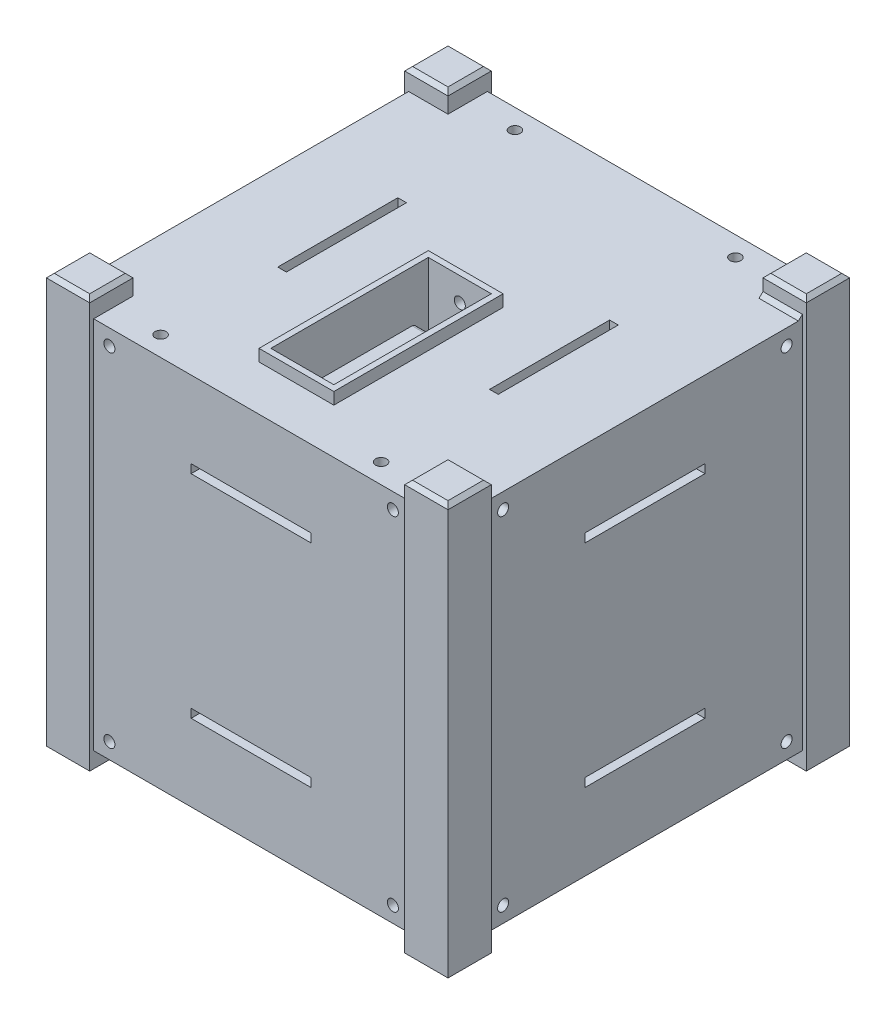
SolidWorks part; units mm, degrees
ref_plane "Front Plane" through (0, 0, 0) normal (0, 0, 1) x (1, 0, 0)
ref_plane "Top Plane" through (0, 0, 0) normal (0, 1, 0) x (1, 0, 0)
ref_plane "Right Plane" through (0, 0, 0) normal (1, 0, 0) x (0, 0, -1)
sketch "Sketch1" plane through (0, 0, 0) normal (0, 1, 0) x (1, 0, 0)
  line L1 (-50, 50) -> (50, 50)
  line L2 (-50, 50) -> (-50, -50)
  line L3 (-50, -50) -> (50, -50)
  line L4 (50, 50) -> (50, -50)
  line L5 (-50, 50) -> (50, -50) construction
  line L6 (-50, -50) -> (50, 50) construction
  point P0 (0, 0)
  dimension "D1" = 100
  dimension "D2" = 100
extrude "Boss-Extrude1" add sketch "Sketch1" along normal blind 95
ref_plane "Plane1" through (0, 100, 0) normal (0, 1, 0) x (1, 0, 0)
sketch "Sketch2" plane through (0, 100, 0) normal (0, 1, 0) x (1, 0, 0)
  line L0 (0, 0) -> (0, 71.0273) construction
  line L1 (-50, 50) -> (-40, 50)
  line L2 (-50, 50) -> (-50, 40)
  line L3 (-50, 40) -> (-40, 40)
  line L4 (-40, 50) -> (-40, 40)
  line L5 (50, 40) -> (40, 40)
  line L6 (40, 50) -> (40, 40)
  line L7 (50, 50) -> (40, 50)
  line L8 (50, 50) -> (50, 40)
  line L9 (0, 0) -> (-74.2097, 0) construction
  line L10 (50, -50) -> (50, -40)
  line L11 (50, -50) -> (40, -50)
  line L12 (40, -50) -> (40, -40)
  line L13 (50, -40) -> (40, -40)
  line L14 (-50, -40) -> (-40, -40)
  line L15 (-40, -50) -> (-40, -40)
  line L16 (-50, -50) -> (-40, -50)
  line L17 (-50, -50) -> (-50, -40)
  dimension "D1" = 10
  dimension "D2" = 10
extrude "Boss-Extrude2" add sketch "Sketch2" against normal blind 105
sketch "Sketch3" plane through (0, 95, 0) normal (0, 1, 0) x (1, 0, 0)
  line L0 (0, 0) -> (-55.4811, 0) construction
  line L1 (0, 0) -> (0, -56.887) construction
  line L3 (50, -40) -> (40, -40) construction
  circle A0 centre (-28, -45) radius 1.4
  circle A1 centre (28, -45) radius 1.4
  circle A2 centre (28, 45) radius 1.4
  circle A3 centre (-28, 45) radius 1.4
  dimension "D1" = 2.8
  dimension "D2" = 28
  dimension "D3" = 85
extrude "Cut-Extrude1" cut sketch "Sketch3" against normal blind 10
sketch "Sketch4" plane through (0, 100, 0) normal (0, 1, 0) x (1, 0, 0)
  line L0 (-50, 50) -> (-50, 40) construction
  line L1 (-40, 40) -> (-51, 40)
  line L2 (-40, 40) -> (-40, 51)
  line L3 (-40, 51) -> (-51, 51)
  line L4 (-51, 40) -> (-51, 51)
  line L5 (40, 50) -> (-40, 50) construction
  line L6 (0, 0) -> (0, 60.0537) construction
  line L7 (0, 0) -> (-61.4769, 0) construction
  line L8 (40, 51) -> (51, 51)
  line L9 (51, 40) -> (51, 51)
  line L10 (40, 40) -> (51, 40)
  line L11 (40, 40) -> (40, 51)
  line L12 (40, -40) -> (40, -51)
  line L13 (40, -40) -> (51, -40)
  line L14 (51, -40) -> (51, -51)
  line L15 (40, -51) -> (51, -51)
  line L16 (-40, -51) -> (-51, -51)
  line L17 (-51, -40) -> (-51, -51)
  line L18 (-40, -40) -> (-51, -40)
  line L19 (-40, -40) -> (-40, -51)
  dimension "D1" = 1
  dimension "D2" = 1
extrude "Boss-Extrude3" add sketch "Sketch4" against normal up to surface (105 mm away) up to face at (-45, -5, -45)
sketch "Sketch5" plane through (0, 0, 50) normal (0, 0, 1) x (1, 0, 0)
  line L0 (0, 95) -> (0, 43.7031) construction
  line L1 (-40, 95) -> (40, 95) construction
  line L2 (40, 47.5) -> (-59.8843, 47.5) construction
  line L3 (40, 0) -> (40, 95) construction
  line L4 (-40, 95) -> (-40, 0) construction
  circle A0 centre (-36, 91) radius 1.4
  circle A1 centre (36, 91) radius 1.4
  circle A2 centre (36, 4) radius 1.4
  circle A3 centre (-36, 4) radius 1.4
  dimension "D1" = 2.8
  dimension "D2" = 4
  dimension "D3" = 4
extrude "Cut-Extrude2" cut sketch "Sketch5" against normal blind 10
mirror "Mirror1" about plane through (0, 0, 0) normal (0, 0, 1) of "Cut-Extrude2"
sketch "Sketch6" plane through (-50, 0, 0) normal (-1, 0, 0) x (0, 0, 1)
  line L0 (-40, 95) -> (-40, 0) construction
  line L1 (-40, 95) -> (40, 95) construction
  line L2 (0, 95) -> (0, 40.4022) construction
  line L3 (-40, 47.5) -> (36.0105, 47.5) construction
  line L4 (-40, -5) -> (-40, 100) construction
  circle A0 centre (-36, 91) radius 1.4
  circle A1 centre (36, 91) radius 1.4
  circle A2 centre (36, 4) radius 1.4
  circle A3 centre (-36, 4) radius 1.4
  dimension "D1" = 2.8
  dimension "D2" = 4
  dimension "D3" = 4
extrude "Cut-Extrude3" cut sketch "Sketch6" against normal blind 10
mirror "Mirror2" about plane through (0, 0, 0) normal (1, 0, 0) of "Cut-Extrude3"
ref_plane "Plane2" through (0, 47.5, 0) normal (0, 1, 0) x (1, 0, 0)
mirror "Mirror3" about plane through (0, 47.5, 0) normal (0, 1, 0) of "Cut-Extrude1"
chamfer "Chamfer1" distance 1 angle 45 33 edges at (-45.5, -5, 51) (-40, -5, 45.5) (-45.5, -5, 40) (-51, -5, 45.5) (40, -5, 45.5) (45.5, -5, 51) (51, -5, 45.5) (45.5, -5, 40) (45.5, -5, -51) (40, -5, -45.5) (45.5, -5, -40) (51, -5, -45.5) (-40, -5, -45.5) (-45.5, -5, -51) (-51, -5, -45.5) (-45.5, -5, -40) (45.5, 100, 51) (40, 100, 45.5) (45.5, 100, 40) (51, 100, 45.5) (40, 100, -45.5) (45.5, 100, -51) (51, 100, -45.5) (45.5, 100, -40) (-45.5, 100, -40) (-51, 100, -45.5) (-45.5, 100, -51) (-40, 100, -45.5) (-40, 100, 45.5) (-45.5, 100, 51) (-51, 100, 45.5) (-45.5, 100, 40) (45, 95, -40)
sketch "Sketch7" plane through (0, 95, 0) normal (0, 1, 0) x (1, 0, 0)
  line L0 (9.5, 4.5) -> (9.5, -38.5)
  line L1 (-8, 3) -> (8, 3)
  line L2 (-8, 3) -> (-8, -37)
  line L3 (-8, -37) -> (8, -37)
  line L4 (8, 3) -> (8, -37)
  line L5 (-9.5, -38.5) -> (9.5, -38.5)
  line L6 (-9.5, 4.5) -> (-9.5, -38.5)
  line L7 (-9.5, 4.5) -> (9.5, 4.5)
  dimension "D1" = 8
  dimension "D2" = 8
  dimension "D3" = 3
  dimension "D4" = 40
  dimension "D5" = 1.5
extrude "Boss-Extrude4" add sketch "Sketch7" along normal blind 3
sketch "Sketch8" plane through (0, 95, 0) normal (0, 1, 0) x (1, 0, 0)
  line L4 (-8, 3) -> (-8, -37)
  line L5 (-8, -37) -> (8, -37)
  line L6 (8, -37) -> (8, 3)
  line L7 (8, 3) -> (-8, 3)
  line L8 (-8, 3) -> (-8, -37)
  line L9 (-8, -37) -> (8, -37)
  line L10 (8, -37) -> (8, 3)
  line L11 (8, 3) -> (-8, 3)
  dimension "D1" = 0
extrude "Cut-Extrude4" cut sketch "Sketch8" against normal blind 10
chamfer "Chamfer2" distance 13 angle 45 1 edges at (0, 85, 37)
sketch "Sketch9" plane through (0, 85, 0) normal (0, 1, 0) x (1, 0, 0)
  line L0 (8, -24) -> (8, 3) construction
  line L1 (-8, 3) -> (8, 3)
  line L2 (-8, 3) -> (-8, -0.1)
  line L3 (-8, -0.1) -> (8, -0.1)
  line L4 (8, 3) -> (8, -0.1)
  dimension "D1" = 3.1
extrude "Cut-Extrude5" cut sketch "Sketch9" against normal blind 10
fillet "Fillet1" radius 1 1 edges at (0, 85, 0.1)
sketch "Sketch10" plane through (0, 0, -3) normal (0, 0, 1) x (1, 0, 0)
  line L0 (8, 98) -> (-8, 98) construction
  line L1 (-8, 98) -> (-8, 75) construction
  circle A0 centre (0, 92) radius 1.4
  dimension "D1" = 2.8
  dimension "D2" = 6
  dimension "D3" = 8
extrude "Cut-Extrude6" cut sketch "Sketch10" against normal blind 10
sketch "Sketch12" plane through (-50, 0, 0) normal (-1, 0, 0) x (0, 0, 1)
  line L0 (-40, 95) -> (40, 95) construction
  line L1 (-15.25, 75.5) -> (15.25, 75.5)
  line L2 (-15.25, 75.5) -> (-15.25, 73.3)
  line L3 (-15.25, 73.3) -> (15.25, 73.3)
  line L4 (15.25, 75.5) -> (15.25, 73.3)
  line L5 (-15.25, 75.5) -> (15.25, 73.3) construction
  line L6 (-15.25, 73.3) -> (15.25, 75.5) construction
  line L7 (0, 95) -> (0, 60.126) construction
  line L8 (-51, 47.5) -> (62.2361, 47.5) construction
  line L9 (-51, -4) -> (-51, 99) construction
  line L10 (-15.25, 21.7) -> (15.25, 21.7)
  line L11 (15.25, 19.5) -> (15.25, 21.7)
  line L12 (-15.25, 19.5) -> (15.25, 19.5)
  line L13 (-15.25, 19.5) -> (-15.25, 21.7)
  point P0 (0, 74.4)
  dimension "D1" = 19.5
  dimension "D2" = 2.2
  dimension "D3" = 30.5
extrude "Cut-Extrude7" cut sketch "Sketch12" against normal blind 3
mirror "Mirror4" about plane through (0, 0, 0) normal (1, 0, 0) of "Cut-Extrude7"
sketch "Sketch13" plane through (0, 0, 50) normal (0, 0, 1) x (1, 0, 0)
  line L0 (0, 95) -> (0, 46.2553) construction
  line L1 (-40, 95) -> (40, 95) construction
  line L2 (-51, 47.5) -> (61.8656, 47.5) construction
  line L3 (-15.25, 75.5) -> (15.25, 75.5)
  line L4 (-15.25, 75.5) -> (-15.25, 73.3)
  line L5 (-15.25, 73.3) -> (15.25, 73.3)
  line L6 (15.25, 75.5) -> (15.25, 73.3)
  line L7 (-15.25, 75.5) -> (15.25, 73.3) construction
  line L8 (-15.25, 73.3) -> (15.25, 75.5) construction
  line L9 (-51, -4) -> (-51, 99) construction
  line L10 (-15.25, 21.7) -> (15.25, 21.7)
  line L11 (15.25, 19.5) -> (15.25, 21.7)
  line L12 (-15.25, 19.5) -> (15.25, 19.5)
  line L13 (-15.25, 19.5) -> (-15.25, 21.7)
  point P5 (0, 74.4)
  dimension "D1" = 30.5
  dimension "D2" = 2.2
  dimension "D3" = 19.5
extrude "Cut-Extrude8" cut sketch "Sketch13" against normal blind 3
mirror "Mirror5" about plane through (0, 0, 0) normal (0, 0, 1) of "Cut-Extrude8"
sketch "Sketch14" plane through (0, 95, 0) normal (0, 1, 0) x (1, 0, 0)
  line L0 (-50, 0) -> (73.3052, 0) construction
  line L1 (-50, 40) -> (-50, -40) construction
  line L2 (0, 50) -> (0, -6.1969) construction
  line L3 (40, 50) -> (-40, 50) construction
  line L4 (28, 15.25) -> (25.8, 15.25)
  line L5 (-28, -15.25) -> (-25.8, -15.25)
  line L6 (-28, -15.25) -> (-28, 15.25)
  line L7 (-28, 15.25) -> (-25.8, 15.25)
  line L8 (-25.8, -15.25) -> (-25.8, 15.25)
  line L9 (-28, -15.25) -> (-25.8, 15.25) construction
  line L10 (-28, 15.25) -> (-25.8, -15.25) construction
  line L11 (25.8, -15.25) -> (25.8, 15.25)
  line L12 (28, -15.25) -> (25.8, -15.25)
  line L13 (28, -15.25) -> (28, 15.25)
  point P9 (-26.9, 0)
  dimension "D1" = 30.5
  dimension "D2" = 2.2
  dimension "D3" = 22
extrude "Cut-Extrude9" cut sketch "Sketch14" against normal blind 3
mirror "Mirror6" about plane through (0, 47.5, 0) normal (0, 1, 0) of "Cut-Extrude9"
sketch "Sketch15" plane through (0, 0, 0) normal (1, 0, 0) x (0, 0, -1)
  line L0 (-40, 0) -> (40, 0) construction
  line L1 (-45, 70) -> (45, 70)
  line L2 (-45, 70) -> (-45, 12)
  line L3 (-45, 12) -> (45, 12)
  line L4 (45, 70) -> (45, 12)
  line L5 (-45, 70) -> (45, 12) construction
  line L6 (-45, 12) -> (45, 70) construction
  line L7 (-51, -4) -> (-51, 99) construction
  line L8 (51, -4) -> (51, 99) construction
  line L9 (-40, 95) -> (39, 95) construction
  point P0 (0, 41)
  dimension "D1" = 12
  dimension "D2" = 6
  dimension "D3" = 6
  dimension "D4" = 25
extrude "Cut-Extrude10" cut sketch "Sketch15" against normal offset from surface 6 and the other way offset from surface 6 up to face at (-51, 47.5, -45.5) other way up to face at (51, 47.5, 45.5)
sketch "Sketch16" plane through (0, 0, 0) normal (0, 0, 1) x (1, 0, 0)
  line L0 (45, 57.0064) -> (-45, 57.0064)
  line L1 (51, -4) -> (51, 99) construction
  line L2 (-51, -4) -> (-51, 99) construction
  line L3 (45, 57.0064) -> (45, 83)
  line L4 (45, 83) -> (13, 83)
  line L5 (13, 83) -> (13, 67.0064)
  line L6 (13, 67.0064) -> (-13, 67.0064)
  line L7 (-13, 67.0064) -> (-13, 83)
  line L8 (-13, 83) -> (-45, 83)
  line L9 (-45, 83) -> (-45, 57.0064)
  line L10 (-40, 95) -> (40, 95) construction
  dimension "D1" = 6
  dimension "D2" = 6
  dimension "D3" = 57.0064
  dimension "D4" = 12
  dimension "D5" = 32
  dimension "D7" = 10
extrude "Cut-Extrude11" cut sketch "Sketch16" along normal up to surface and the other way up to surface up to face at (0, 41, 45) other way up to face at (0, 41, -45)
chamfer "Chamfer3" distance 4 angle 45 2 edges at (-13, 70, 0) (13, 70, 0)
